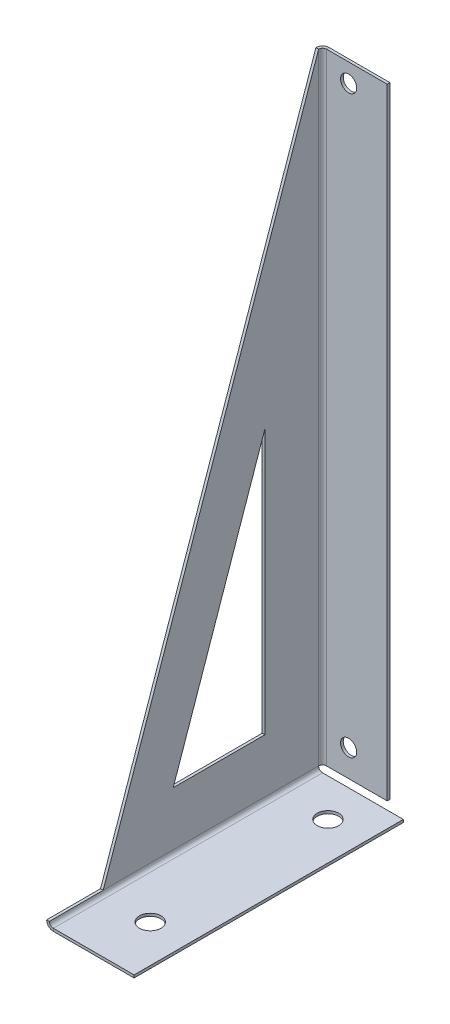
SolidWorks part; units mm, degrees
note: The reader was unsure of these and kept them because the rebuilt part matched: flange length of "Edge-Flange1", "Edge-Flange2".
ref_plane "Front Plane" through (0, 0, 0) normal (0, 0, 1) x (1, 0, 0)
ref_plane "Top Plane" through (0, 0, 0) normal (0, 1, 0) x (1, 0, 0)
ref_plane "Right Plane" through (0, 0, 0) normal (1, 0, 0) x (0, 0, -1)
sketch "Sketch2" plane through (0, 0, 0) normal (0, 1, 0) x (1, 0, 0)
  line L1 (-15, 0) -> (0, 0)
  line L2 (-15, 0) -> (-15, -50)
  line L3 (-15, -50) -> (0, -50)
  line L4 (0, 0) -> (0, -50)
  dimension "D1" = 50
  dimension "D2" = 15
sheet metal parameters "Sheet-Metal1" thickness 0.5 parameters "D1"=0.7366
base flange "Base-Flange1" sketch "Sketch2" thickness 0.5 reverse thickness direction no parameters "D1"=0.7366
edge flange "Edge-Flange1" sketch "Sketch7" flange angle 90 flange length 116 flange position bend outside bend radius 0.7366 thickness 0.5 parameters "D6"=10
sketch "Sketch7" plane through (-15, 0, 0) normal (-1, 0, 0) x (0, 0, 1)
  line L0 (0, 0) -> (50, 0) construction
  line L1 (0, 0) -> (50, 0)
  line L2 (0, 0) -> (0, 116)
  line L3 (0, 116) -> (50, 116)
  line L4 (50, 116) -> (50, 0)
bend "EdgeBend1" bend radius 0.7366 bend angle 90 parameters "D5"=1
sketch "Sketch8" plane through (-16.2366, 0, 0) normal (-1, 0, 0) x (0, 0, 1)
  line L1 (50, 0.7366) -> (0, 0.7366) construction
  line L2 (40, 0.7366) -> (0, 116)
  line L4 (0, 116) -> (50, 116)
  line L5 (50, 116) -> (50, 0.7366)
  line L6 (50, 0.7366) -> (40, 0.7366)
  dimension "D1" = 10
extrude "Cut-Extrude1" cut sketch "Sketch8" against normal blind 10
edge flange "Edge-Flange2" sketch "Sketch11" flange angle 90 flange length 12 flange position bend outside bend radius 0.7366 thickness 0.5 parameters "D6"=10
sketch "Sketch11" plane through (-15.7366, 0, 0) normal (0, 0, -1) x (0, 1, 0)
  line L0 (116, 0) -> (0.7366, 0) construction
  line L1 (116, 0) -> (0.7366, 0)
  line L2 (0.7366, 0) -> (0.7366, 12)
  line L3 (0.7366, 12) -> (116, 12)
  line L4 (116, 12) -> (116, 0)
bend "EdgeBend2" bend radius 0.7366 bend angle 90 parameters "D5"=2
sketch "Sketch12" plane through (-16.2366, 0, 0) normal (-1, 0, 0) x (0, 0, 1)
  line L0 (10, 59.8511) -> (27, 10.7366)
  line L1 (0, 116) -> (0, 0.7366) construction
  line L2 (40, 0.7366) -> (0, 0.7366) construction
  line L9 (10, 10.7366) -> (27, 10.7366)
  line L10 (10, 10.7366) -> (10, 59.8511)
  dimension "D1" = 49.1145
  dimension "D2" = 17
  dimension "D3" = 10
  dimension "D4" = 10
extrude "Cut-Extrude2" cut sketch "Sketch12" against normal blind 10
sketch "Sketch13" plane through (0, 0, -1.2366) normal (0, 0, -1) x (-1, 0, 0)
  line L0 (3.7366, 0.7366) -> (15, 0.7366) construction
  line L1 (15, 116) -> (15, 0.7366) construction
  circle A0 centre (10.9, 5.7366) radius 1.5
  dimension "D3" = 3
  dimension "D1" = 5
  dimension "D2" = 4.1
extrude "Cut-Extrude3" cut sketch "Sketch13" against normal blind 10
sketch "Sketch14" plane through (0, 0, -0.7366) normal (0, 0, 1) x (1, 0, 0)
  line L0 (-15, 116) -> (-15, 0.7366) construction
  circle A0 centre (-10.9, 112.5366) radius 1.5
  circle A1 centre (-10.9, 5.7366) radius 1.5 construction
  dimension "D1" = 106.8
  dimension "D2" = 4.1
extrude "Cut-Extrude4" cut sketch "Sketch14" against normal blind 10
sketch "Sketch15" plane through (0, 0, 0) normal (0, 1, 0) x (1, 0, 0)
  line L0 (0, -50) -> (0, 0) construction
  line L1 (-15, -50) -> (0, -50) construction
  circle A0 centre (-7, -40) radius 2
  point P0 (-7.5, -50)
  dimension "D3" = 4
  dimension "D1" = 10
  dimension "D2" = 7
extrude "Cut-Extrude5" cut sketch "Sketch15" against normal blind 12
sketch "Sketch16" plane through (0, 0, 0) normal (0, 1, 0) x (1, 0, 0)
  line L0 (0, -50) -> (0, 0) construction
  line L1 (0, 0) -> (-15, 0) construction
  circle A0 centre (-7, -7) radius 2
  dimension "D2" = 4
  dimension "D1" = 7
  dimension "D3" = 7
extrude "Cut-Extrude6" cut sketch "Sketch16" against normal blind 12
flat pattern "Flat-Pattern1" [suppressed]
sketch "Bend-Lines1" plane through (0, 0, 0) normal (0, 1, 0) x (1, 0, 0)
  line L0 (-16.5497, 0.7749) -> (-131.8131, 0.7749) construction
  line L1 (-15.7749, -50) -> (-15.7749, 0) construction
  line L2 (-16.5497, 0.7749) -> (-131.8131, 0.7749) construction
  line L3 (-15.7749, -50) -> (-15.7749, 0) construction
sketch3d "Bounding-Box1" [suppressed]
  line L0 (0, -50, 0) -> (-131.8131, -50, 0) construction
  line L1 (0, 12.8131, 0) -> (-131.8131, 12.8131, 0) construction
  line L2 (0, -50, 0) -> (0, 12.8131, 0) construction
  line L3 (-131.8131, -50, 0) -> (-131.8131, 12.8131, 0) construction
bend of the flat pattern "Flatten-<EdgeBend1>1"
bend of the flat pattern "Flatten-<EdgeBend2>1"
